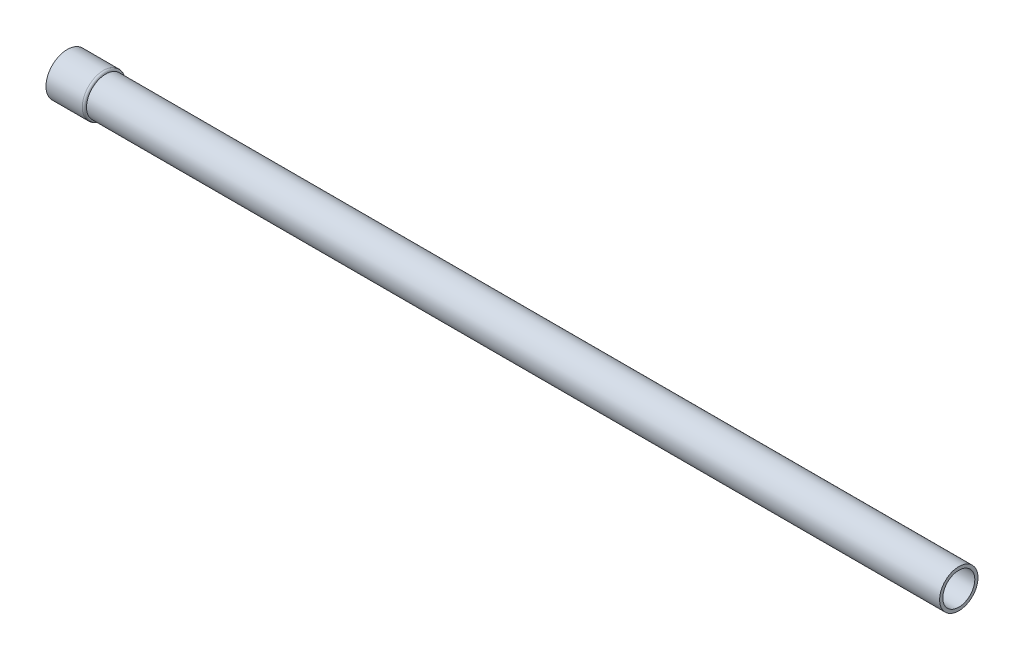
SolidWorks part; units mm, degrees
ref_plane "前基準面" through (0, 0, 0) normal (0, 0, 1) x (1, 0, 0)
ref_plane "上基準面" through (0, 0, 0) normal (0, 1, 0) x (1, 0, 0)
ref_plane "右基準面" through (0, 0, 0) normal (1, 0, 0) x (0, 0, -1)
sketch "草圖1" plane through (0, 0, 0) normal (1, 0, 0) x (0, 0, -1)
  circle A0 centre (0, 0) radius 7.5
  circle A1 centre (0, 0) radius 9
  dimension "D1" = 15
  dimension "D2" = 18
extrude "填料-伸長2" add sketch "草圖1" along normal blind 400
ref_plane "平面1" through (-18, 0, 0) normal (-1, 0, 0) x (0, 0, 1)
sketch "草圖3" plane through (-18, 0, 0) normal (-1, 0, 0) x (0, 0, 1)
  circle A0 centre (0, 0) radius 10
  circle A1 centre (0, 0) radius 8.5
  dimension "D1" = 20
  dimension "D2" = 1.5
extrude "填料-伸長3" add sketch "草圖3" against normal up to surface (18 mm away) up to face at (0, 0, -9)
fillet "圓角2" radius 1 1 edges at (0, 0, -10)
